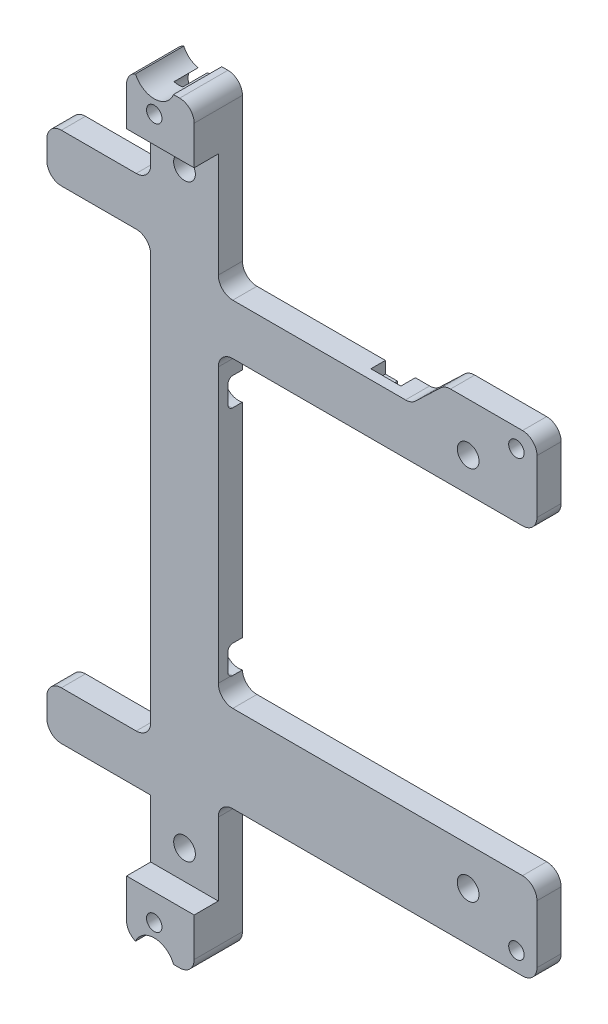
SolidWorks part; units mm, degrees
ref_plane "Front Plane" through (0, 0, 0) normal (1, 0, 0) x (0, 1, 0)
ref_plane "Top Plane" through (0, 0, 0) normal (0, 0, 1) x (0, 1, 0)
ref_plane "Right Plane" through (0, 0, 0) normal (0, 1, 0) x (-1, 0, 0)
sketch "Sketch1" plane through (0, 0, 0) normal (0, 0, 1) x (0, 1, 0)
  line L0 (-38.86, 0.005) -> (38.86, -0.005) construction
  line L1 (-38.86, 0.005) -> (38.86, -0.005) construction
  line L2 (0, 0) -> (0, 106.5364) construction
  line L8 (-55, 65.745) -> (-55, 87.245)
  line L13 (-67.5, 65.745) -> (67.5, 51.745) construction
  line L14 (-67.5, 51.745) -> (67.5, 65.745) construction
  line L15 (-55, 87.245) -> (-45, 87.245)
  line L16 (-45, 87.245) -> (-45, 65.745)
  line L17 (-45, 65.745) -> (45, 65.745)
  line L18 (45, 87.245) -> (45, 65.745)
  line L19 (55, 87.245) -> (45, 87.245)
  line L20 (55, 65.745) -> (55, 87.245)
  line L22 (62.0223, 59.9423) -> (59.9389, 57.5466) construction
  line L23 (62.1784, 57.7039) -> (59.7816, 59.7861) construction
  line L45 (42.2651, 11.7705) -> (42.2651, 52.7631) construction
  line L47 (-48.9476, 51.745) -> (-48.9476, -14.255)
  line L48 (-48.9476, -14.255) -> (-30.9476, -14.255)
  line L49 (-30.9476, -14.255) -> (-30.9476, 51.745)
  line L50 (-30.9476, 51.745) -> (31.792, 51.745)
  line L51 (31.792, 51.745) -> (31.792, -14.255)
  line L52 (31.792, -14.255) -> (48.8866, -14.255)
  line L53 (48.8866, -14.255) -> (48.8866, 4.8443)
  line L54 (48.8866, 4.8443) -> (42.2651, 11.7705)
  line L55 (42.2651, 11.7705) -> (42.2651, 51.745)
  line L60 (-55, 65.745) -> (-78, 65.745)
  line L62 (-78, 65.745) -> (-78, 51.745)
  line L63 (-78, 51.745) -> (-48.9476, 51.745)
  line L64 (78, 65.745) -> (78, 51.745)
  line L65 (55, 65.745) -> (78, 65.745)
  line L66 (78, 51.745) -> (42.2651, 51.745)
  circle A0 centre (-38.86, 0.005) radius 2.25
  circle A1 centre (38.86, -0.005) radius 2.25
  circle A2 centre (-60.99, 58.735) radius 2.25
  circle A3 centre (60.98, 58.745) radius 2.25
  circle A8 centre (-45, -9.995) radius 1.6
  circle A10 centre (45, -9.995) radius 1.6
  circle A14 centre (60.98, 58.745) radius 1.5874 construction
  circle A15 centre (-72.5, 60.005) radius 3
  circle A17 centre (72.5, 60.005) radius 3
  point P28 (0, 58.745)
  dimension "D1" = 4.5
  dimension "D4" = 4.5
  dimension "D5" = 4.5
  dimension "D10" = 4.5
  dimension "D11" = 3.2
  dimension "D13" = 45
  dimension "D12" = 10
  dimension "D14" = 6
  dimension "D16" = 70
  dimension "D2" = 77.72
  dimension "D3" = 0.01
  dimension "D6" = 22.13
  dimension "D7" = 58.73
  dimension "D8" = 99.84
  dimension "D9" = 58.74
  dimension "D15" = 72.5
  dimension "D17" = 14
  dimension "D18" = 23
  dimension "D19" = 10
  dimension "D20" = 90
  dimension "D21" = 21.5
  dimension "D22" = 66
  dimension "D23" = 18
  dimension "D24" = 62.7397
extrude "Boss-Extrude1" add sketch "Sketch1" along normal blind 5
sketch "Sketch4" plane through (0, 0, 5) normal (0, 0, 1) x (1, 0, 0)
  line L0 (-59.9423, 62.0223) -> (-57.5466, 59.9389) construction
  line L1 (-57.7039, 62.1784) -> (-59.7861, 59.7816) construction
  line L2 (-52.7631, 68.2675) -> (-66.1639, 68.2675) construction
  line L3 (-66.1639, 68.2675) -> (-66.1639, 50.4408) construction
  line L4 (-66.1639, 50.4408) -> (-106.6121, 50.4408) construction
  line L5 (-106.6121, 50.4408) -> (-106.6121, 34.0894) construction
  line L6 (-106.6121, 34.0894) -> (-66.1639, 34.0894) construction
  line L7 (-66.1639, 34.0894) -> (-66.1639, -39.7992) construction
  line L8 (-66.1639, -39.7992) -> (-105.8744, -39.7992) construction
  line L9 (-105.8744, -39.7992) -> (-105.8744, -55.1671) construction
  line L10 (-105.8744, -55.1671) -> (-65.4262, -55.1671) construction
  line L11 (-65.4262, -55.1671) -> (-65.4262, -83.2031) construction
  line L12 (-65.4262, -83.2031) -> (-51.2429, -83.2031) construction
  line L13 (-51.2429, -83.2031) -> (-51.2429, -48.9476) construction
  line L14 (-51.2429, -48.9476) -> (16.9144, -48.9476) construction
  line L15 (16.9144, -48.9476) -> (16.9144, -14.8647) construction
  line L16 (16.9144, -14.8647) -> (-49.6702, -14.8647) construction
  line L17 (-49.6702, -14.8647) -> (-49.6702, 30.0022) construction
  line L18 (-49.6702, 30.0022) -> (-49.6702, 31.792) construction
  line L19 (-49.6702, 31.792) -> (21.8605, 31.792) construction
  line L20 (21.8605, 31.792) -> (21.8605, 50.4408) construction
  line L21 (21.8605, 50.4408) -> (-3.2186, 50.4408) construction
  line L22 (-3.2186, 50.4408) -> (-11.7705, 42.2651) construction
  line L23 (-11.7705, 42.2651) -> (-52.7631, 42.2651) construction
  line L24 (-52.7631, 42.2651) -> (-52.7631, 68.2675) construction
  line L25 (-53.5293, 13.6559) -> (-53.5293, 8.5989) construction
  line L26 (-53.5293, 13.6559) -> (-57.5472, 13.6559) construction
  line L27 (-57.5472, 13.6559) -> (-57.5472, 8.5989) construction
  line L28 (-53.5293, 8.5989) -> (-57.5472, 8.5989) construction
  line L29 (-53.5293, 13.6559) -> (-57.5472, 8.5989) construction
  line L30 (-57.5472, 13.6559) -> (-53.5293, 8.5989) construction
  line L31 (-30.5241, 33.1453) -> (-30.5241, 30.4388) construction
  line L32 (-30.5241, 33.1453) -> (-34.3522, 33.1453) construction
  line L33 (-34.3522, 33.1453) -> (-34.3522, 30.4388) construction
  line L34 (-30.5241, 30.4388) -> (-34.3522, 30.4388) construction
  line L35 (-30.5241, 33.1453) -> (-34.3522, 30.4388) construction
  line L36 (-34.3522, 33.1453) -> (-30.5241, 30.4388) construction
  line L37 (-34.5262, 33.1453) -> (-34.5262, 30.4388) construction
  line L38 (-34.5262, 33.1453) -> (-37.7452, 33.1453) construction
  line L39 (-37.7452, 33.1453) -> (-37.7452, 30.4388) construction
  line L40 (-34.5262, 30.4388) -> (-37.7452, 30.4388) construction
  line L41 (-34.5262, 33.1453) -> (-37.7452, 30.4388) construction
  line L42 (-37.7452, 33.1453) -> (-34.5262, 30.4388) construction
  line L43 (-16.3911, 40.3217) -> (-16.3911, 37.7641) construction
  line L44 (-16.3911, 40.3217) -> (-19.6245, 40.3217) construction
  line L45 (-19.6245, 40.3217) -> (-19.6245, 37.7641) construction
  line L46 (-16.3911, 37.7641) -> (-19.6245, 37.7641) construction
  line L47 (-16.3911, 40.3217) -> (-19.6245, 37.7641) construction
  line L48 (-19.6245, 40.3217) -> (-16.3911, 37.7641) construction
  line L49 (-15.9373, 44.8094) -> (-15.9373, 40.9494) construction
  line L50 (-15.9373, 44.8094) -> (-22.1441, 44.8094) construction
  line L51 (-22.1441, 44.8094) -> (-22.1441, 40.9494) construction
  line L52 (-15.9373, 40.9494) -> (-22.1441, 40.9494) construction
  line L53 (-15.9373, 44.8094) -> (-22.1441, 40.9494) construction
  line L54 (-22.1441, 44.8094) -> (-15.9373, 40.9494) construction
  circle A0 centre (-58.745, 60.98) radius 1.5874 construction
  circle A1 centre (-52.5383, 22.8611) radius 3 construction
  circle A2 centre (-52.5383, -25.1544) radius 3 construction
  circle A3 centre (-10.615, -39.3884) radius 1 construction
  circle A4 centre (-10.615, -46.9884) radius 1 construction
  circle A5 centre (-19.6245, -25.1544) radius 3 construction
  circle A6 centre (-58.745, 60.98) radius 2.25 construction
  point P33 (-55.5383, 11.1274)
  point P44 (-32.4381, 31.792)
  point P49 (-36.1357, 31.792)
  point P54 (-18.0078, 39.0429)
  point P59 (-19.0407, 42.8794)
sketch "Sketch5" plane through (0, 0, 0) normal (0, 0, -1) x (1, 0, 0)
  line L0 (-16.3911, -39.8089) -> (-15.9373, -39.8089)
  line L1 (-57.5472, -8.5989) -> (-53.5293, -8.5989)
  line L2 (-57.5472, -8.5989) -> (-57.5472, -13.6559)
  line L3 (-57.5472, -13.6559) -> (-53.5293, -13.6559)
  line L4 (-53.5293, -8.5989) -> (-53.5293, -13.6559)
  line L5 (-57.5472, -8.5989) -> (-53.5293, -13.6559) construction
  line L6 (-57.5472, -13.6559) -> (-53.5293, -8.5989) construction
  line L7 (-37.7452, -30.4388) -> (-30.5241, -30.4388)
  line L8 (-37.7452, -30.4388) -> (-37.7452, -33.1453)
  line L9 (-37.7452, -33.1453) -> (-30.5241, -33.1453)
  line L10 (-30.5241, -30.4388) -> (-30.5241, -33.1453)
  line L11 (-19.6245, -37.7641) -> (-16.3911, -37.7641)
  line L12 (-19.6245, -37.7641) -> (-19.6245, -39.8089)
  line L14 (-16.3911, -37.7641) -> (-16.3911, -39.8089)
  line L15 (-22.1441, -39.8089) -> (-19.6245, -39.8089)
  line L16 (-22.1441, -39.8089) -> (-22.1441, -44.8094)
  line L17 (-22.1441, -44.8094) -> (-15.9373, -44.8094)
  line L18 (-15.9373, -39.8089) -> (-15.9373, -44.8094)
  circle A0 centre (-52.5383, -22.8611) radius 3
  circle A1 centre (-52.5383, 25.1544) radius 3
  circle A2 centre (-10.615, 46.9884) radius 1
  circle A3 centre (-10.615, 39.3884) radius 1
  point P6 (-55.5383, -11.1274)
extrude "Cut-Extrude1" cut sketch "Sketch5" against normal blind 3
sketch "Sketch7" plane through (0, 0, 5) normal (0, 0, 1) x (1, 0, 0)
  line L0 (-51.745, 42.2651) -> (-51.745, 78) construction
  line L1 (-65.745, 78) -> (-51.745, 78)
  line L2 (-65.745, 78) -> (-65.745, 67)
  line L3 (-65.745, 67) -> (-51.745, 67)
  line L4 (-51.745, 78) -> (-51.745, 67)
  line L5 (0, 0) -> (-129.6565, 0) construction
  line L6 (-51.745, -78) -> (-51.745, -67)
  line L7 (-65.745, -67) -> (-51.745, -67)
  line L8 (-65.745, -78) -> (-65.745, -67)
  line L9 (-65.745, -78) -> (-51.745, -78)
  dimension "D1" = 11
extrude "Boss-Extrude2" add sketch "Sketch7" along normal blind 5
sketch "Sketch8" plane through (0, 0, 10) normal (0, 0, 1) x (1, 0, 0)
  line L0 (0, 0) -> (-41.2457, 0) construction
  circle A0 centre (-60.005, 72.5) radius 1.6
  circle A1 centre (-60.005, -72.5) radius 1.6
  dimension "D1" = 3.2
extrude "Cut-Extrude2" cut sketch "Sketch8" against normal blind 10
fillet "Fillet1" radius 3 21 edges at (-51.745, -30.9476, 2.5) (-65.745, -45, 2.5) (-87.245, -45, 2.5) (-87.245, -55, 2.5) (14.255, -48.9476, 2.5) (14.255, -30.9476, 2.5) (-51.745, 31.792, 2.5) (-65.745, 45, 2.5) (-87.245, 45, 2.5) (-87.245, 55, 2.5) (-11.7705, 42.2651, 2.5) (-4.8443, 48.8866, 2.5) (14.255, 31.792, 2.5) (14.255, 48.8866, 2.5) (-51.745, 42.2651, 2.5) (-51.745, 78, 5) (-65.745, 55, 2.5) (-65.745, 78, 5) (-51.745, -48.9476, 2.5) (-51.745, -78, 5) (-65.745, -78, 5)
fillet "Fillet2" radius 1 15 edges at (-11.615, -46.9884, 3) (-11.615, -39.3884, 3) (-18.0078, 37.7641, 3) (-16.3911, 38.7865, 3) (-19.6245, 38.7865, 3) (-20.8843, 39.8089, 3) (-30.5241, 32.4687, 3) (-37.7452, 32.4687, 3) (-34.1347, 33.1453, 3) (-55.5383, 22.8611, 3) (-55.5383, -25.1552, 3) (-55.5383, 8.5989, 3) (-53.5293, 11.1274, 3) (-55.5383, 13.6559, 3) (-57.5472, 11.1274, 3)
sketch "Sketch9" plane through (0, 0, 10) normal (0, 0, 1) x (1, 0, 0)
  line L0 (0, 0) -> (-47.8889, 0) construction
  circle A0 centre (-60.005, 79.5) radius 4.25
  circle A2 centre (-60.005, -79.5) radius 4.25
extrude "Cut-Extrude3" cut sketch "Sketch9" against normal blind 10
sketch "Sketch10" plane through (0, 0, 0) normal (0, 0, -1) x (1, 0, 0)
  circle A0 centre (9.995, 45) radius 3
  circle A1 centre (9.995, -45) radius 3
  dimension "D1" = 6
  dimension "D2" = 6
extrude "Cut-Extrude4" cut sketch "Sketch10" against normal blind 2
